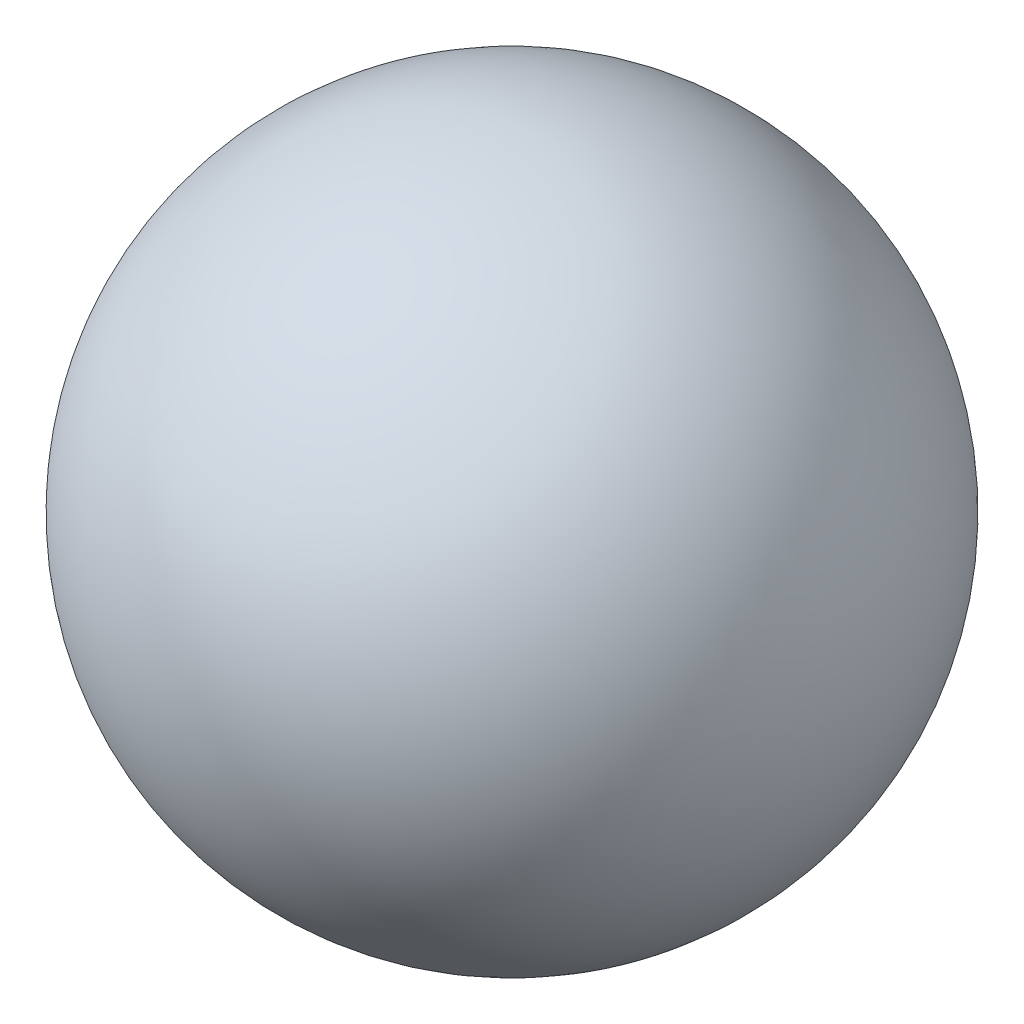
SolidWorks part; units mm, degrees
ref_plane "前视基准面" through (0, 0, 0) normal (0, 0, 1) x (1, 0, 0)
ref_plane "上视基准面" through (0, 0, 0) normal (0, 1, 0) x (1, 0, 0)
ref_plane "右视基准面" through (0, 0, 0) normal (1, 0, 0) x (0, 0, -1)
sketch "草图1" plane through (0, 0, 0) normal (0, 0, 1) x (1, 0, 0)
  line L0 (0, 0) -> (-10.0106, 29.4514)
  line L1 (-10.0106, 29.4514) -> (14.0934, -41.463)
  circle A0 centre (0, 0) radius 25
revolve "旋转4" add sketch "草图1" angle 360 about L1 region at (-10.0459, -3.4146, 0)
